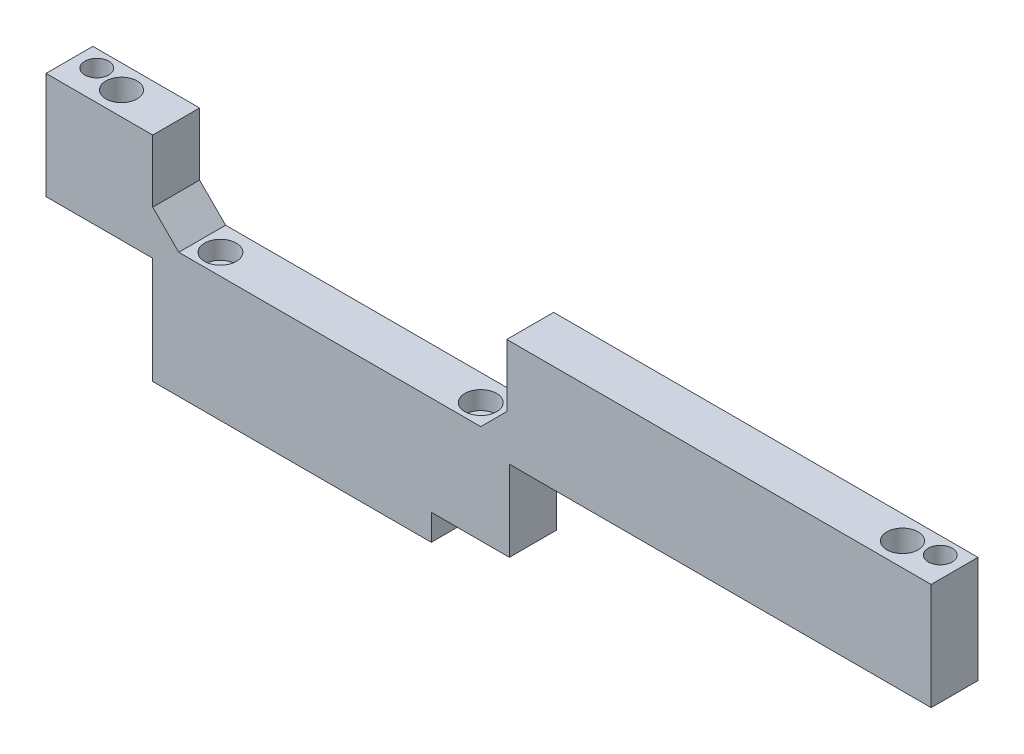
SolidWorks part; units mm, degrees
material "ABS"
ref_plane "Top Plane" through (0, 0, 0) normal (0, 0, 1) x (1, 0, 0)
ref_plane "Front Plane" through (0, 0, 0) normal (0, 1, 0) x (1, 0, 0)
ref_plane "Right Plane" through (0, 0, 0) normal (1, 0, 0) x (0, 0, -1)
sketch "Sketch1" plane through (0, 0, 0) normal (0, 0, 1) x (1, 0, 0)
  line L0 (-85, 18.5852) -> (85, 18.5852)
  line L1 (-85, 18.5852) -> (-85, -1.9148)
  line L2 (-85, -1.9148) -> (-64.5, -1.9148)
  line L3 (85, 18.5852) -> (85, -1.9148)
  line L4 (85, -1.9148) -> (4, -1.9148)
  line L5 (-64.5, -1.9148) -> (-64.5, -22.4148)
  line L6 (-64.5, -22.4148) -> (-11, -22.4148)
  line L7 (-11, -22.4148) -> (-11, -17.4148)
  line L8 (-11, -17.4148) -> (4, -17.4148)
  line L9 (4, -17.4148) -> (4, -1.9148)
  point P3 (0, 18.5852)
  dimension "D1" = 170
  dimension "D2" = 20.5
  dimension "D3" = 20.5
  dimension "D4" = 20.5
  dimension "D5" = 81
  dimension "D6" = 20.5
  dimension "D7" = 5
  dimension "D8" = 15
extrude "Boss-Extrude1" add sketch "Sketch1" along normal blind 9
sketch "Sketch7" plane through (0, 18.5852, 0) normal (0, 1, 0) x (1, 0, 0)
  circle A0 centre (-75, -4.5) radius 1.75
  circle A1 centre (75, -4.5) radius 1.75
  point P7 (92.667, -5.3981)
  dimension "D5" = 3.5
  dimension "D6" = 3.5
  dimension "D1" = 4.5
  dimension "D2" = 4.5
  dimension "D3" = 150
  dimension "D4" = 75
extrude "Cut-Extrude5" cut sketch "Sketch7" against normal through all
sketch "Sketch8" plane through (0, 18.5852, 0) normal (0, 1, 0) x (1, 0, 0)
  circle A0 centre (-75, -4.5) radius 3
  circle A1 centre (75, -4.5) radius 3
  dimension "D1" = 6
  dimension "D2" = 6
extrude "Cut-Extrude6" cut sketch "Sketch8" against normal blind 10
sketch "Sketch9" plane through (0, 18.5852, 0) normal (0, 1, 0) x (1, 0, 0)
  line L0 (85, 0) -> (-85, 0) construction
  line L1 (-64.5, 0) -> (3.5, 0)
  line L2 (-64.5, 0) -> (-64.5, -9)
  line L3 (-64.5, -9) -> (3.5, -9)
  line L4 (3.5, 0) -> (3.5, -9)
  line L5 (85, -9) -> (-85, -9) construction
  line L6 (-85, -9) -> (-85, 0) construction
  dimension "D1" = 68
  dimension "D2" = 20.5
extrude "Cut-Extrude7" cut sketch "Sketch9" against normal blind 17
chamfer "Chamfer1" distance 5 angle 45 2 edges at (3.5, 1.5852, 4.5) (-64.5, 1.5852, 4.5)
sketch "Sketch10" plane through (0, 1.5852, 0) normal (0, 1, 0) x (1, 0, 0)
  line L0 (-1.5, -9) -> (-1.5, 0) construction
  line L1 (-1.5, 0) -> (-59.5, 0) construction
  circle A0 centre (-55.5, -5) radius 3.05
  circle A1 centre (-5.5, -5) radius 3.05
  dimension "D1" = 6.1
  dimension "D2" = 6.1
  dimension "D3" = 50
  dimension "D4" = 4
  dimension "D5" = 5
  dimension "D6" = 5
extrude "Cut-Extrude8" cut sketch "Sketch10" against normal blind 3.5
sketch "Sketch11" plane through (0, 18.5852, 0) normal (0, 1, 0) x (1, 0, 0)
  line L0 (-64.5, 0) -> (-85, 0) construction
  line L1 (85, 0) -> (3.5, 0) construction
  line L2 (-85, -9) -> (-85, 0) construction
  line L3 (85, -9) -> (85, 0) construction
  circle A0 centre (-81, -3.25) radius 2.3
  circle A1 centre (81, -3.25) radius 2.3
  point P0 (-81, -3.25)
  point P1 (81, -3.25)
  dimension "D5" = 4.6
  dimension "D6" = 4.6
  dimension "D1" = 3.25
  dimension "D2" = 3.25
  dimension "D3" = 4
  dimension "D4" = 4
extrude "Cut-Extrude9" cut sketch "Sketch11" against normal blind 10
sketch "Sketch12" plane through (0, -1.9148, 0) normal (0, -1, 0) x (1, 0, 0)
  circle A0 centre (-75, -6.5) radius 8
  circle A1 centre (75, -6) radius 7.5
  dimension "D2" = 16
  dimension "D3" = 15
  dimension "D1" = 150
  dimension "D4" = 75
  dimension "D5" = 6.5
  dimension "D6" = 6
extrude "Cut-Extrude13" cut sketch "Sketch12" against normal blind 5
